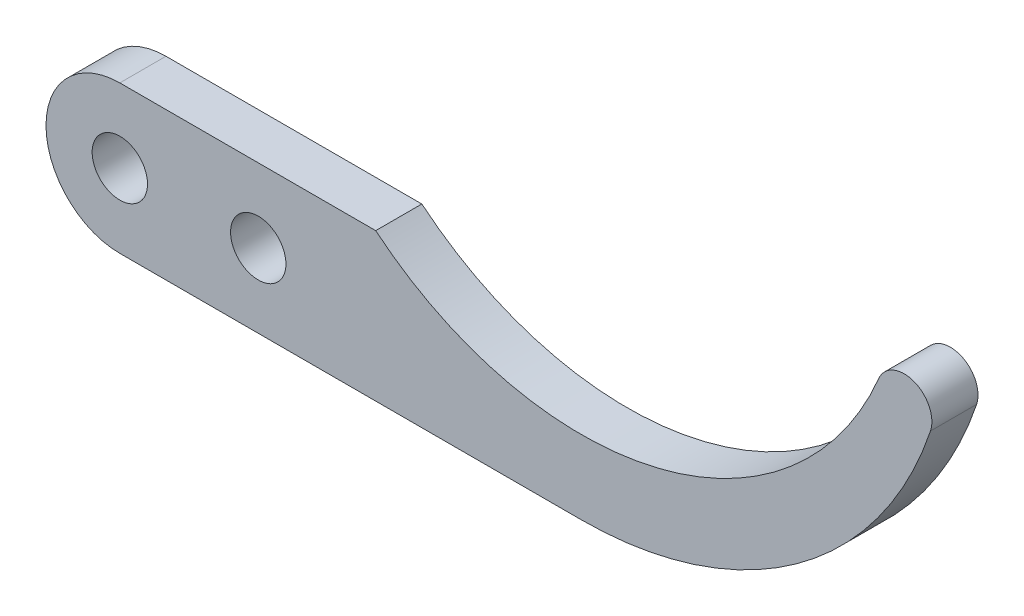
SolidWorks part; units mm, degrees
ref_plane "Plan de face" through (0, 0, 0) normal (0, 0, 1) x (1, 0, 0)
ref_plane "Plan de dessus" through (0, 0, 0) normal (0, 1, 0) x (1, 0, 0)
ref_plane "Plan de droite" through (0, 0, 0) normal (1, 0, 0) x (0, 0, -1)
sketch "Esquisse1" plane through (0, 0, 0) normal (0, 0, 1) x (1, 0, 0)
  line L0 (0, 0) -> (80, 0) construction
  line L1 (20, 0) -> (20, 23.8674) construction
  line L2 (0, 0) -> (0, 35) construction
  line L3 (0, 35) -> (50, 35) construction
  line L4 (0, 8) -> (20, 8)
  line L5 (82.2368, 21.3697) -> (85, 20.2014) construction
  line L6 (20, 8) -> (27.7289, 8)
  line L7 (0, -8) -> (50, -8)
  line L8 (50, 35) -> (50, -8) construction
  line L9 (0, 8) -> (-15, 8) construction
  line L10 (0, 0) -> (-15, 0) construction
  line L11 (0, -8) -> (-15, -8) construction
  circle A0 centre (0, 0) radius 3
  arc A1 (0, 8) -> (0, -8) centre (0, 0) ccw
  circle A2 centre (50, 35) radius 35 construction
  arc A3 (27.7289, 8) -> (82.2368, 21.3697) centre (50, 35) ccw
  arc A4 (82.2368, 21.3697) -> (87.8451, 19.25) centre (85, 20.2014) cw
  arc A5 (50, -8) -> (87.8451, 19.25) centre (50, 31.9049) ccw
  circle A6 centre (15, 0) radius 3
  arc A7 (-15, 8) -> (-15, -8) centre (-15, 0) ccw construction
  circle A8 centre (-15, 0) radius 3 construction
  dimension "D3" = 6
  dimension "D4" = 35
  dimension "D6" = 70
  dimension "D7" = 3
  dimension "D8" = 8
  dimension "D9" = 35
  dimension "D10" = 15
  dimension "D11" = 8
  dimension "D1" = 20
  dimension "D2" = 80
  dimension "D5" = 50
  dimension "D12" = 15
extrude "Boss.-Extru.1" add sketch "Esquisse1" along normal blind 5
